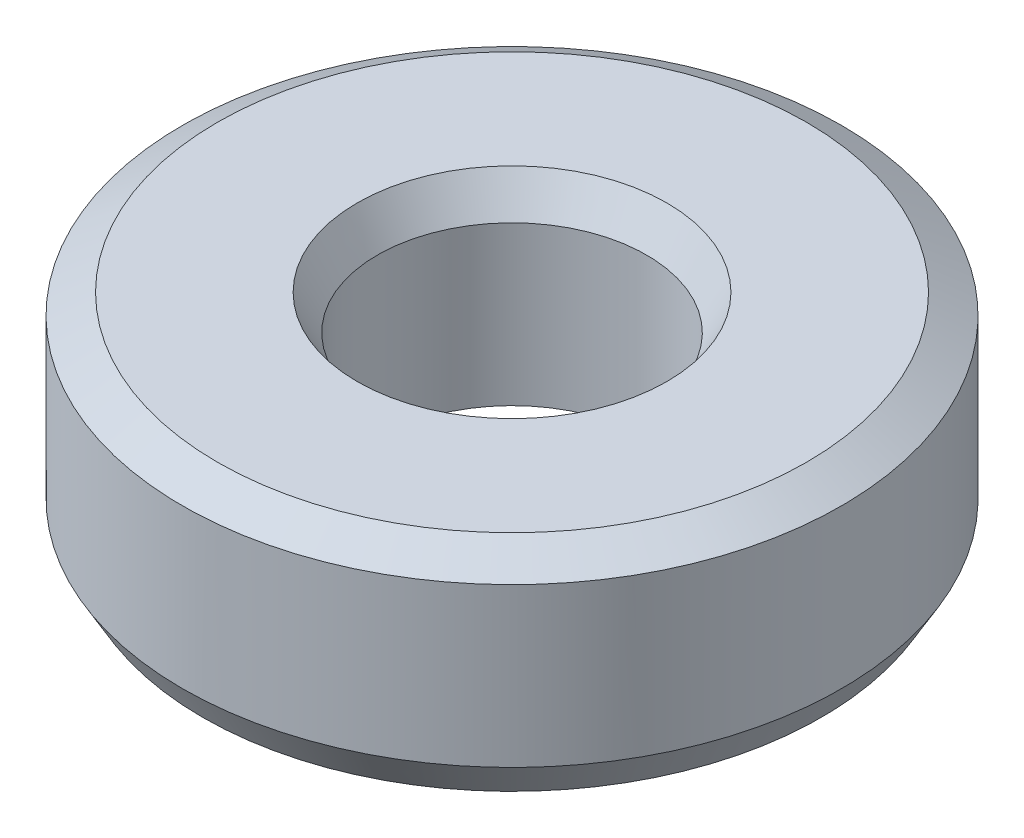
SolidWorks part; units mm, degrees
ref_plane "Front Plane" through (0, 0, 0) normal (0, 0, 1) x (1, 0, 0)
ref_plane "Top Plane" through (0, 0, 0) normal (0, 1, 0) x (1, 0, 0)
ref_plane "Right Plane" through (0, 0, 0) normal (1, 0, 0) x (0, 0, -1)
sketch "Sketch1" plane through (0, 0, 0) normal (0, 1, 0) x (1, 0, 0)
  circle A0 centre (0, 0) radius 52.5
  dimension "SLEEVE_OD" = 105
extrude "Boss-Extrude1" add sketch "Sketch1" along normal blind 34.025
sketch "Sketch2" plane through (0, 0, 0) normal (0, 1, 0) x (1, 0, 0)
  circle A0 centre (0, 0) radius 21.4424
  dimension "BORE_D" = 42.8847
extrude "Cut-Extrude1" cut sketch "Sketch2" along normal through all
chamfer "Chamfer1" distance 3.2216 angle 60 4 edges at (0, 34.025, 21.4424) (0, 0, 21.4424) (0, 0, 52.5) (0, 34.025, 52.5) first distance on face at (0, 34.025, 21.4424) first distance on face at (0, 0, 21.4424) first distance on face at (0, 34.025, 52.5)
